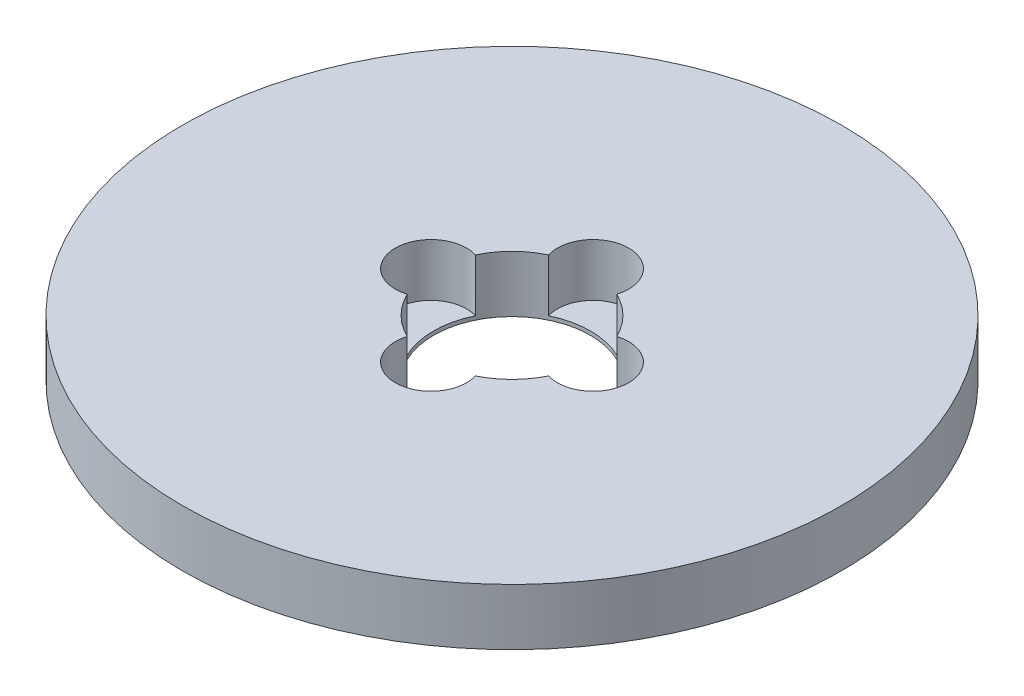
SolidWorks part; units mm, degrees
ref_plane "Front Plane" through (0, 0, 0) normal (0, 0, 1) x (1, 0, 0)
ref_plane "Top Plane" through (0, 0, 0) normal (0, 1, 0) x (1, 0, 0)
ref_plane "Right Plane" through (0, 0, 0) normal (1, 0, 0) x (0, 0, -1)
sketch "Sketch1" plane through (0, 0, 0) normal (0, 1, 0) x (1, 0, 0)
  circle A0 centre (0, 0) radius 52.5
  dimension "FLANGE_OD" = 105
extrude "Boss-Extrude1" add sketch "Sketch1" along normal blind 9
sketch "Sketch2" plane through (0, 0, 0) normal (0, 1, 0) x (1, 0, 0)
  circle A0 centre (0, 0) radius 12.5
  dimension "BORE_D" = 25
extrude "Cut-Extrude1" cut sketch "Sketch2" along normal through all
sketch "Sketch3" plane through (0, 9, 0) normal (0, 1, 0) x (1, 0, 0)
  circle A0 centre (0, 0) radius 12.9114 construction
  circle A1 centre (-12.9114, 0) radius 5.6777
  dimension "BOLT_D" = 11.3555
  dimension "BOLT_PCD" = 25.8227
extrude "Cut-Extrude2" cut sketch "Sketch3" against normal blind 8.3967
pattern_circular "CirPattern1" count 4 over 360 about axis through (0, 0, 0) along (0, 1, 0) of "Cut-Extrude2"
